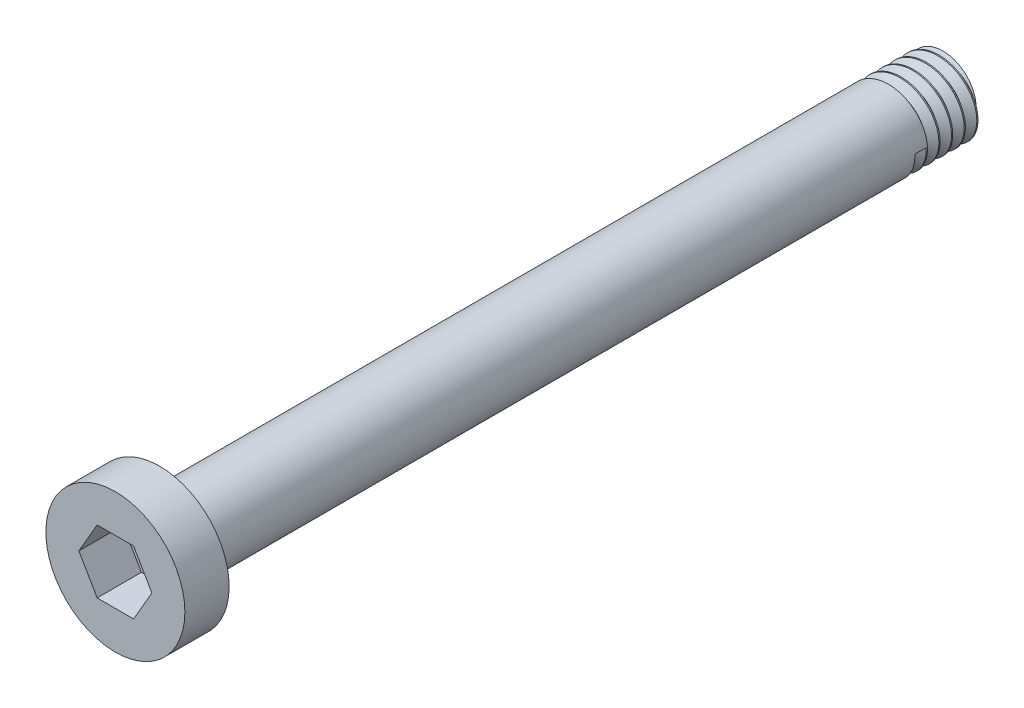
SolidWorks part; units mm, degrees
material "AISI 304"
ref_plane "Alzado" through (0, 0, 0) normal (0, 0, 1) x (1, 0, 0)
ref_plane "Planta" through (0, 0, 0) normal (0, 1, 0) x (1, 0, 0)
ref_plane "Vista lateral" through (0, 0, 0) normal (1, 0, 0) x (0, 0, -1)
ref_plane "Plano1" through (0, 0, 4.2) normal (0, 0, 1) x (1, 0, 0)
sketch "Sk_Cana" plane through (0, 0, 4.2) normal (0, 0, 1) x (1, 0, 0)
  circle A0 centre (-36, -62) radius 3
extrude "Cana" add sketch "Sk_Cana" along normal blind 62.2
cosmetic thread "Rosca cosmética1" parameters "D1"=62.2, "D2"=4.7731
ref_plane "Plano2" through (0, 0, 66.4) normal (0, 0, 1) x (1, 0, 0)
sketch "Sk_Cabeza" plane through (0, 0, 66.4) normal (0, 0, 1) x (1, 0, 0)
  line L0 (-33.1132, -62) -> (-34.5566, -59.5)
  line L1 (-34.5566, -59.5) -> (-37.4434, -59.5)
  line L2 (-37.4434, -59.5) -> (-38.8868, -62)
  line L3 (-38.8868, -62) -> (-37.4434, -64.5)
  line L4 (-37.4434, -64.5) -> (-34.5566, -64.5)
  line L5 (-34.5566, -64.5) -> (-33.1132, -62)
  circle A0 centre (-36, -62) radius 5.5
extrude "Cabeza" add sketch "Sk_Cabeza" along normal blind 3.5
ref_plane "Plano3" through (0, 0, 4.2) normal (0, 0, 1) x (1, 0, 0)
sketch "Sk_Helice_Rosca_M6x1" plane through (0, 0, 4.2) normal (0, 0, 1) x (1, 0, 0)
  circle A0 centre (-36, -62) radius 3
curve "Helice_Rosca_M6x1" pitch 1 height 5 radius 3 centre (-36, -62, 4.2) axis (0, 0, 1) start towards (1, 0, 0)
ref_plane "Plano5" through (0, -62, 0) normal (0, 1, 0) x (1, 0, 0)
sketch "Sk_perfil_Rosca_M6x1" plane through (0, -62, 0) normal (0, 1, 0) x (1, 0, 0)
  line L0 (-32.7, -3.5268) -> (-32.7, -4.8732)
  line L1 (-32.7, -4.8732) -> (-33.6134, -4.2)
  line L2 (-33.6134, -4.2) -> (-32.7, -3.5268)
sweep "Rosca_M6x1" cut profiles "Sk_perfil_Rosca_M6x1" path "Helice_Rosca_M6x1" align with end faces yes
